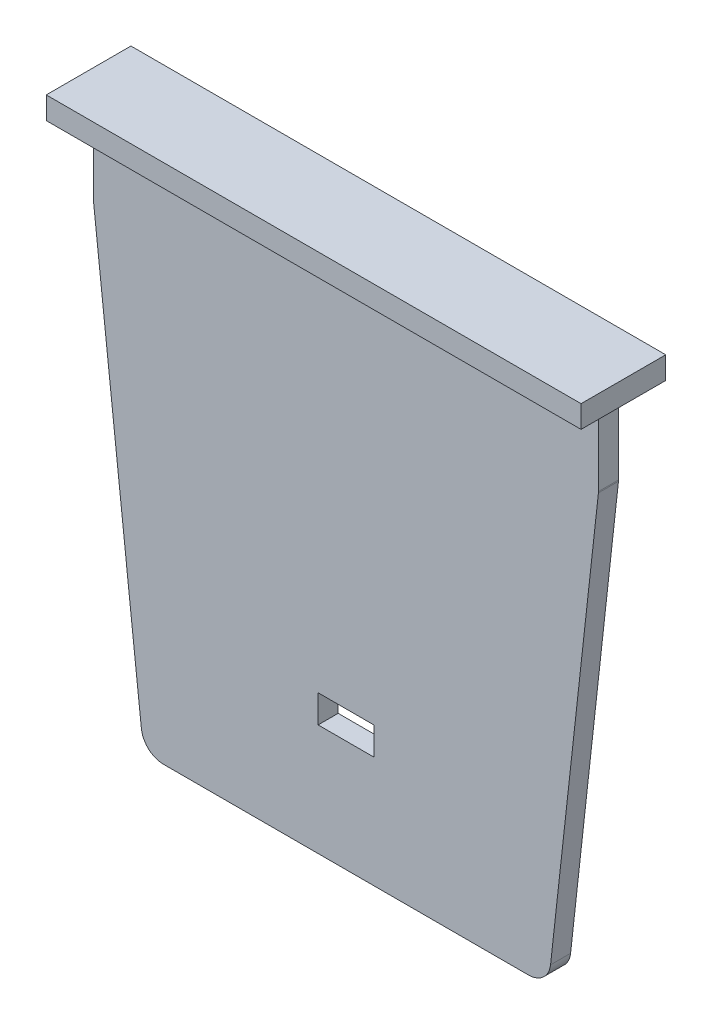
SolidWorks part; units mm, degrees
ref_plane "Front Plane" through (0, 0, 0) normal (0, 0, 1) x (1, 0, 0)
ref_plane "Top Plane" through (0, 0, 0) normal (0, 1, 0) x (1, 0, 0)
ref_plane "Right Plane" through (0, 0, 0) normal (1, 0, 0) x (0, 0, -1)
sketch "Sketch2" plane through (0, 0, 0) normal (0, 0, -1) x (-1, 0, 0)
  line L0 (-4.9216, 54.5793) -> (-4.9216, -59.013) construction
  line L6 (-62.4874, 48.8485) -> (52.6441, 48.8485)
  line L7 (52.6441, 48.8485) -> (41.7132, -49.932)
  line L8 (36.664, -54.4533) -> (-46.5073, -54.4533)
  line L9 (-62.4874, 48.8485) -> (-51.5564, -49.932)
  arc A4 (41.7132, -49.932) -> (36.664, -54.4533) centre (36.664, -49.3733) cw
  arc A5 (-51.5564, -49.932) -> (-46.5073, -54.4533) centre (-46.5073, -49.3733) ccw
  point P27 (-4.9216, -54.4533)
  point P28 (-4.9216, 48.8485)
  dimension "D4" = 98.7805
  dimension "D6" = 48.8485
  dimension "D11" = 5.08
  dimension "D2" = 115.1315
  dimension "D3" = 83.1712
  dimension "D5" = 36.664
extrude "Boss-Extrude1" add sketch "Sketch2" along normal blind 4.572
sketch "Sketch3" plane through (0, 48.8485, 0) normal (0, 1, 0) x (1, 0, 0)
  line L0 (-52.6441, 4.572) -> (-52.6441, 0)
  line L1 (-52.6441, 4.572) -> (62.4874, 4.572)
  line L2 (-52.6441, 0) -> (62.4874, 0)
  line L3 (62.4874, 4.572) -> (62.4874, 0)
  line L4 (62.4874, 4.572) -> (62.4874, 0) construction
  dimension "D1" = 0
extrude "Boss-Extrude2" add sketch "Sketch3" along normal blind 17.78
sketch "Sketch4" plane through (0, 66.6285, 0) normal (0, 1, 0) x (1, 0, 0)
  line L0 (-52.6441, 0) -> (62.4874, 0) construction
  line L1 (62.4874, 0) -> (62.4874, 4.572) construction
  line L2 (-52.6441, 0) -> (62.4874, 0) construction
  line L3 (62.4874, -7.366) -> (62.4874, 11.938) construction
  line L4 (-52.6441, -7.366) -> (-52.6441, 37.8542) construction
  line L5 (0, -33.6753) -> (0, 37.8542) construction
  line L10 (-56.0384, 11.938) -> (-56.0384, -7.366)
  line L11 (-56.0384, 11.938) -> (82.2468, 11.938) construction
  line L12 (62.4874, -7.366) -> (-56.0384, -7.366) construction
  line L13 (-56.0384, 11.938) -> (65.8816, 11.938)
  line L14 (-56.0384, -7.366) -> (65.8816, -7.366)
  line L15 (65.8816, 11.938) -> (65.8816, -7.366)
  line L16 (62.4874, 4.572) -> (-52.6441, 4.572) construction
  dimension "D1" = 7.366
  dimension "D2" = 7.366
  dimension "D3" = 3.3942
  dimension "D4" = 3.3942
fillet "Fillet1" radius 2.54 2 edges at (62.4874, 48.8485, -2.286) (-52.6441, 48.8485, -2.286)
extrude "Boss-Extrude4" add sketch "Sketch4" along normal blind 5.08
sketch "Sketch5" plane through (0, 0, -4.572) normal (0, 0, -1) x (-1, 0, 0)
  line L0 (-4.9216, 66.6285) -> (-4.9216, -54.4533) construction
  line L2 (-65.8816, 66.6285) -> (56.0384, 66.6285) construction
  line L3 (-46.5073, -54.4533) -> (36.664, -54.4533) construction
  line L4 (1.4284, -22.7033) -> (-11.2716, -22.7033)
  line L5 (-11.2716, -22.7033) -> (-11.2716, -29.0533)
  line L6 (-11.2716, -29.0533) -> (1.4284, -29.0533)
  line L7 (1.4284, -22.7033) -> (1.4284, -29.0533)
  point P11 (-4.9216, -29.0533)
  point P12 (-4.9216, -22.7033)
  dimension "D1" = 6.35
  dimension "D2" = 6.35
  dimension "D3" = 25.4
extrude "Cut-Extrude1" cut sketch "Sketch5" against normal blind 5.08
